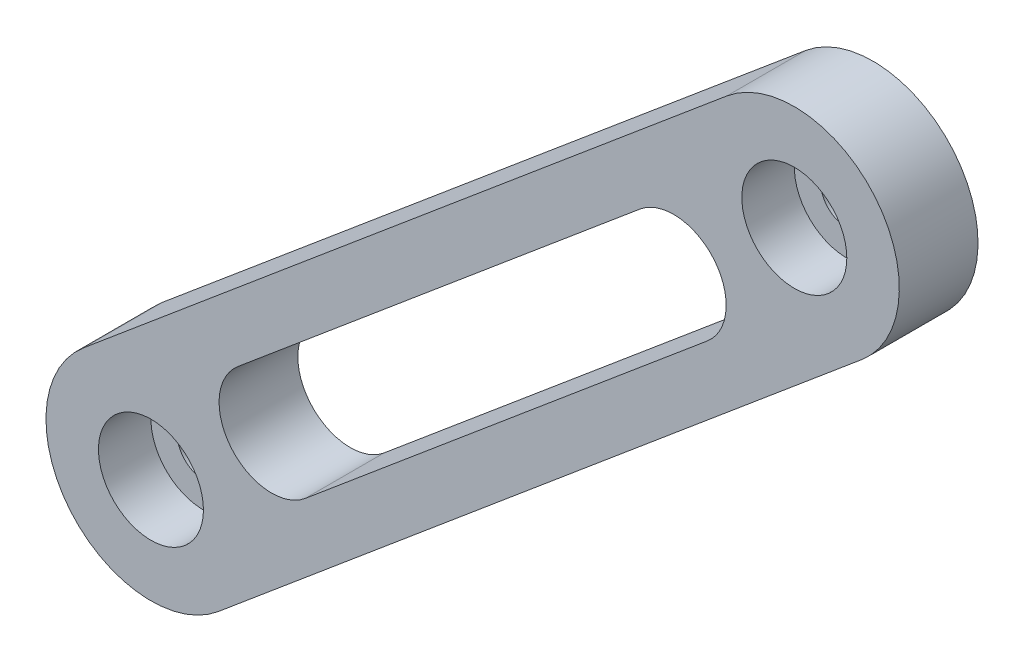
SolidWorks part; units mm, degrees
ref_plane "Front Plane" through (0, 0, 0) normal (0, 0, 1) x (1, 0, 0)
ref_plane "Top Plane" through (0, 0, 0) normal (0, 1, 0) x (1, 0, 0)
ref_plane "Right Plane" through (0, 0, 0) normal (1, 0, 0) x (0, 0, -1)
sketch "Sketch1" plane through (0, 0, 0) normal (0, 0, 1) x (1, 0, 0)
  line L0 (0, 0) -> (179.8502, 0) construction
  line L1 (8.1025, 0) -> (496.1402, 409.5122) construction
  line L2 (496.1402, 409.5122) -> (568.3483, 0) construction
  line L5 (460.3559, 412.643) -> (304.6956, 282.0285)
  line L7 (493.0095, 373.7279) -> (337.3493, 243.1135)
  line L9 (447.4964, 368.6952) -> (350.2087, 287.0612) construction
  line L10 (455.6598, 358.9665) -> (358.3721, 277.3324)
  line L11 (439.333, 378.424) -> (342.0453, 296.79)
  line L12 (321.0225, 262.571) -> (304.6956, 282.0285) construction
  line L13 (321.0225, 262.571) -> (337.3493, 243.1135) construction
  line L14 (460.3559, 412.643) -> (493.0095, 373.7279) construction
  arc A0 (455.6598, 358.9665) -> (439.333, 378.424) centre (447.4964, 368.6952) ccw
  arc A1 (342.0453, 296.79) -> (358.3721, 277.3324) centre (350.2087, 287.0612) ccw
  circle A2 centre (321.0225, 262.571) radius 6.35
  arc A3 (304.6956, 282.0285) -> (337.3493, 243.1135) centre (321.0225, 262.571) ccw
  circle A4 centre (476.6827, 393.1854) radius 6.35
  arc A5 (460.3559, 412.643) -> (493.0095, 373.7279) centre (476.6827, 393.1854) cw
  point P12 (398.8526, 327.8782)
  point P24 (476.6827, 393.1854)
  dimension "D6" = 12.7
  dimension "D7" = 12.7
  dimension "D4" = 25.4
  dimension "D3" = 25.4
  dimension "D1" = 40
  dimension "D2" = 80
  dimension "D5" = 127
  dimension "D8" = 38.1
  dimension "D9" = 38.1
extrude "Boss-Extrude1" add sketch "Sketch1" along normal blind 19.05
sketch "Sketch2" plane through (0, 0, 19.05) normal (0, 0, 1) x (1, 0, 0)
  circle A0 centre (321.0225, 262.571) radius 12.7
  circle A1 centre (476.6827, 393.1854) radius 12.7
  dimension "D1" = 25.4
extrude "Cut-Extrude1" cut sketch "Sketch2" against normal blind 12.7
